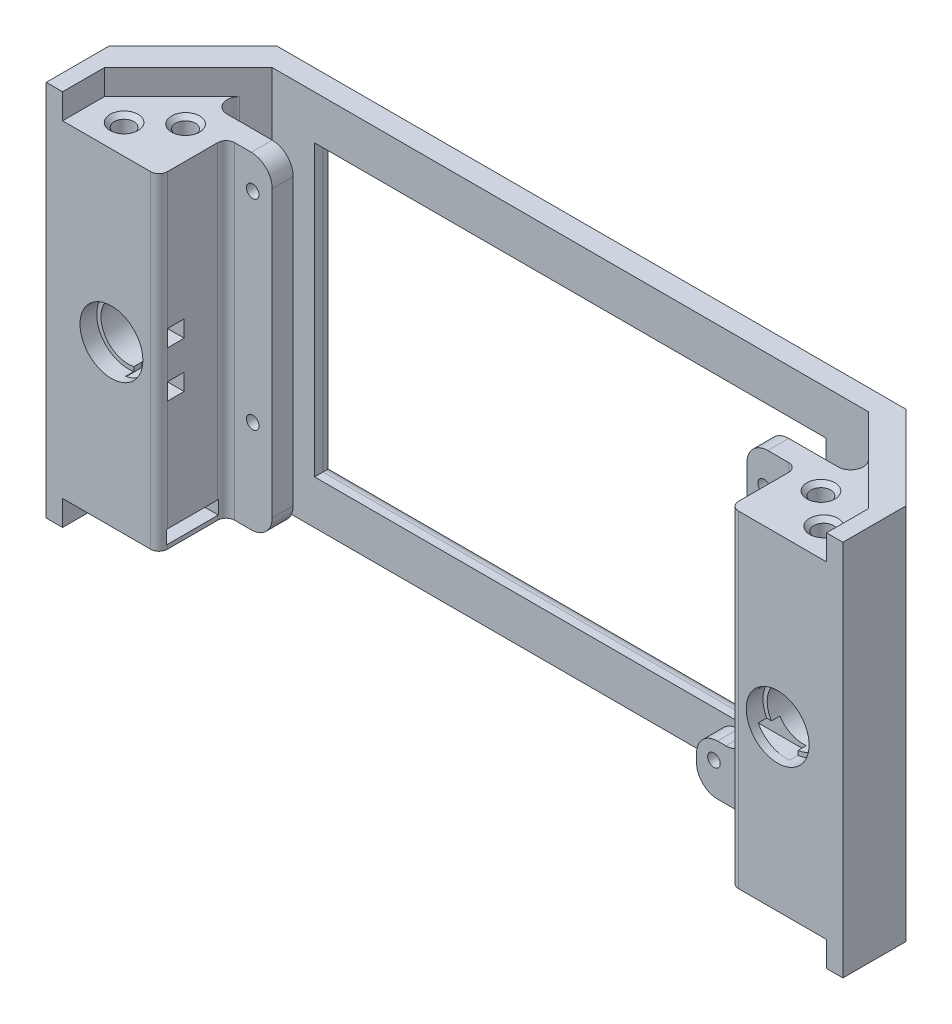
SolidWorks part; units mm, degrees
ref_plane "Front Plane" through (0, 0, 0) normal (0, 0, 1) x (1, 0, 0)
ref_plane "Top Plane" through (0, 0, 0) normal (0, 1, 0) x (1, 0, 0)
ref_plane "Right Plane" through (0, 0, 0) normal (1, 0, 0) x (0, 0, -1)
sketch "Sketch1" plane through (0, 0, 0) normal (0, 0, 1) x (1, 0, 0)
  line L1 (-95, 45) -> (95, 45)
  line L2 (-95, 45) -> (-95, -45)
  line L3 (-95, -45) -> (95, -45)
  line L4 (95, 45) -> (95, -45)
  line L5 (-95, 45) -> (95, -45) construction
  line L6 (-95, -45) -> (95, 45) construction
  line L7 (-61, 34.5) -> (61, 34.5)
  line L8 (-61, 34.5) -> (-61, -34.5)
  line L9 (-61, -34.5) -> (61, -34.5)
  line L10 (61, 34.5) -> (61, -34.5)
  line L11 (-61, 34.5) -> (61, -34.5) construction
  line L12 (-61, -34.5) -> (61, 34.5) construction
  point P0 (0, 0)
  point P6 (0, 0)
  dimension "D1" = 122
  dimension "D2" = 190
  dimension "D3" = 69
  dimension "D4" = 90
extrude "Boss-Extrude1" add sketch "Sketch1" along normal blind 5
sketch "Sketch2" plane through (0, 0, 5) normal (0, 0, 1) x (1, 0, 0)
  line L0 (-95, -45) -> (95, -45) construction
  line L1 (-95, 45) -> (-91.1, 45)
  line L2 (-95, 45) -> (-95, -45)
  line L3 (-95, -45) -> (-91.1, -45)
  line L4 (-91.1, 45) -> (-91.1, -45)
  line L5 (0, 0) -> (0, 45) construction
  line L6 (95, 45) -> (-95, 45) construction
  line L7 (95, -45) -> (91.1, -45)
  line L8 (91.1, 45) -> (91.1, -45)
  line L9 (95, 45) -> (91.1, 45)
  line L10 (95, 45) -> (95, -45)
  dimension "D1" = 3.9
extrude "Boss-Extrude2" add sketch "Sketch2" along normal blind 30
sketch "Sketch3" plane through (0, 45, 0) normal (0, 1, 0) x (1, 0, 0)
  line L0 (-91.1, -35) -> (-91.1, -5) construction
  line L1 (-91.1, -14) -> (-57.1, -14)
  line L2 (-91.1, -14) -> (-91.1, -19)
  line L3 (-91.1, -19) -> (-57.1, -19)
  line L4 (-57.1, -14) -> (-57.1, -19)
  line L5 (91.1, -35) -> (91.1, -5) construction
  line L6 (91.1, -14) -> (44.1, -14)
  line L7 (91.1, -14) -> (91.1, -19)
  line L8 (91.1, -19) -> (44.1, -19)
  line L9 (44.1, -14) -> (44.1, -19)
  line L10 (91.1, -5) -> (-91.1, -5) construction
  dimension "D1" = 9
  dimension "D2" = 9
  dimension "D3" = 5
  dimension "D4" = 5
  dimension "D5" = 34
  dimension "D6" = 47
extrude "Boss-Extrude3" add sketch "Sketch3" against normal up to surface (90 mm away) up to face at (0, -45, 18.75)
sketch "Sketch4" plane through (0, 0, 19) normal (0, 0, 1) x (1, 0, 0)
  line L0 (91.1, -45) -> (91.1, 45) construction
  line L1 (-91.1, 45) -> (91.1, 45)
  line L2 (-91.1, 45) -> (-91.1, 39)
  line L3 (-91.1, 39) -> (91.1, 39)
  line L4 (91.1, 45) -> (91.1, 39)
  line L5 (0, 0) -> (-91.1, 0) construction
  line L6 (-91.1, -45) -> (-91.1, 45) construction
  line L7 (-91.1, -39) -> (91.1, -39)
  line L8 (91.1, -45) -> (91.1, -39)
  line L9 (-91.1, -45) -> (91.1, -45)
  line L10 (-91.1, -45) -> (-91.1, -39)
  dimension "D1" = 6
extrude "Cut-Extrude1" cut sketch "Sketch4" against normal blind 5
sketch "Sketch5" plane through (0, 0, 19) normal (0, 0, 1) x (1, 0, 0)
  line L0 (0, 0) -> (-61.75, 0) construction
  line L1 (-70.2, 37.38) -> (70.2, 37.38) construction
  line L2 (-70.2, 37.38) -> (-70.2, -37.38) construction
  line L3 (-70.2, -37.38) -> (70.2, -37.38) construction
  line L4 (70.2, 37.38) -> (70.2, -37.38) construction
  line L5 (-70.2, 37.38) -> (70.2, -37.38) construction
  line L6 (-70.2, -37.38) -> (70.2, 37.38) construction
  line L7 (-61.75, 0) -> (-61.75, 31.13) construction
  line L8 (-61.75, 0) -> (-61.75, -16.61) construction
  line L9 (48.25, 0) -> (60.23, 0) construction
  line L10 (60.23, 0) -> (60.23, 31.13) construction
  line L11 (0, 0) -> (48.25, 0) construction
  line L12 (48.25, 0) -> (48.25, -31.38) construction
  circle A0 centre (-61.75, 31.13) radius 1.5
  circle A1 centre (-61.75, -16.61) radius 1.5
  circle A2 centre (60.23, 31.13) radius 1.5
  circle A3 centre (48.25, -31.38) radius 1.5
  point P0 (0, 0)
  dimension "D10" = 3
  dimension "D11" = 3
  dimension "D12" = 3
  dimension "D13" = 3
  dimension "D1" = 140.4
  dimension "D2" = 74.76
  dimension "D3" = 61.75
  dimension "D4" = 31.13
  dimension "D5" = 16.61
  dimension "D6" = 60.23
  dimension "D7" = 31.13
  dimension "D8" = 48.25
  dimension "D9" = 31.38
extrude "Cut-Extrude2" cut sketch "Sketch5" against normal up to surface (5 mm away) up to face at (67.6, 0, 14)
sketch "Sketch6" plane through (0, 0, 19) normal (0, 0, 1) x (1, 0, 0)
  line L1 (44.1, 39) -> (56.1, 39)
  line L2 (44.1, 39) -> (44.1, -27)
  line L3 (44.1, -27) -> (56.1, -27)
  line L4 (56.1, 39) -> (56.1, -27)
  dimension "D1" = 12
  dimension "D2" = 66
extrude "Cut-Extrude3" cut sketch "Sketch6" against normal up to surface (5 mm away) up to face at (46.75, -31.38, 14)
fillet "Fillet3" radius 3 4 edges at (-61, 0, 0) (0, -34.5, 0) (61, 0, 0) (0, 34.5, 0)
chamfer "Chamfer6" distance 20 angle 45 4 edges at (91.1, 0, 5) (95, 0, 0) (-95, 0, 0) (-91.1, 0, 5)
sketch "Sketch7" plane through (0, 39, 0) normal (0, 1, 0) x (1, 0, 0)
  line L0 (-85.1, -19) -> (-91.1, -25)
  line L1 (-91.1, -25) -> (-91.1, -35)
  line L2 (-91.1, -35) -> (-68.1, -35)
  line L3 (-68.1, -35) -> (-68.1, -19)
  line L4 (-85.1, -19) -> (-57.1, -19) construction
  line L5 (-68.1, -19) -> (-85.1, -19)
  line L6 (0, 0) -> (0, -5) construction
  line L7 (71.1, -5) -> (-71.1, -5) construction
  line L8 (68.1, -35) -> (68.1, -19)
  line L9 (91.1, -35) -> (68.1, -35)
  line L10 (91.1, -25) -> (91.1, -35)
  line L11 (85.1, -19) -> (91.1, -25)
  line L12 (68.1, -19) -> (85.1, -19)
  dimension "D1" = 23
extrude "Boss-Extrude4" add sketch "Sketch7" against normal up to surface (78 mm away) up to face at (-69.85, -39, 16.5)
fillet "Fillet4" radius 5 6 edges at (-57.1, -39, 16.5) (-57.1, 39, 16.5) (56.1, 39, 16.5) (44.1, -39, 16.5) (44.1, -27, 16.5) (56.1, -27, 16.5)
fillet "Fillet5" radius 2 4 edges at (-68.1, 0, 35) (68.1, 0, 35) (68.1, 0, 19) (-68.1, 0, 19)
fillet "Fillet6" radius 3 2 edges at (-80.1, 0, 14) (80.1, 0, 14)
sketch "Sketch9" plane through (0, 0, 35) normal (0, 0, 1) x (1, 0, 0)
  line L6 (0, 0) -> (0, -45) construction
  line L7 (-71.1, -45) -> (71.1, -45) construction
  line L8 (-95, 45) -> (-95, -45) construction
  line L9 (-95, 39) -> (-79.45, 39) construction
  line L10 (-95, 39) -> (-95, -0.9074) construction
  line L11 (-95, -0.9074) -> (-79.45, -0.9074) construction
  line L12 (-79.45, 39) -> (-79.45, -0.9074) construction
  line L13 (-91.1, 39) -> (-70.1, 39) construction
  circle A0 centre (-79.45, -0.9074) radius 6.5
  circle A1 centre (79.45, -0.9074) radius 6.5
  dimension "D3" = 13
  dimension "D1" = 39.9074
  dimension "D2" = 15.55
extrude "Cut-Extrude4" cut sketch "Sketch9" against normal blind 10
sketch "Sketch10" plane through (0, 0, 35) normal (0, 0, 1) x (1, 0, 0)
  circle A0 centre (-79.45, -0.9074) radius 7.5
  circle A1 centre (79.45, -0.9074) radius 7.5
  dimension "D1" = 15
  dimension "D2" = 15
extrude "Cut-Extrude5" cut sketch "Sketch10" against normal blind 4
sketch "Sketch12" plane through (-68.1, 0, 0) normal (1, 0, 0) x (0, 0, -1)
  line L0 (-33, -4.4074) -> (-29, -4.4074)
  line L1 (-33, 39) -> (-23, 39) construction
  line L2 (-33, 39) -> (-33, -0.9074) construction
  line L3 (-33, -0.9074) -> (-23, -0.9074) construction
  line L4 (-23, 39) -> (-23, -0.9074) construction
  line L5 (-33, 6.5926) -> (-23, 6.5926) construction
  line L6 (-33, 6.5926) -> (-33, -8.4074) construction
  line L7 (-33, -8.4074) -> (-23, -8.4074) construction
  line L8 (-23, 6.5926) -> (-23, -8.4074) construction
  line L9 (-33, 6.5926) -> (-23, -8.4074) construction
  line L10 (-33, -8.4074) -> (-23, 6.5926) construction
  line L11 (-33, 6.5926) -> (-29, 6.5926)
  line L12 (-33, 6.5926) -> (-33, 2.5926)
  line L13 (-33, 2.5926) -> (-29, 2.5926)
  line L14 (-29, 6.5926) -> (-29, 2.5926)
  line L15 (-29, -8.4074) -> (-29, -4.4074)
  line L16 (-33, -8.4074) -> (-29, -8.4074)
  line L17 (-33, -8.4074) -> (-33, -4.4074)
  point P5 (-28, -0.9074)
  dimension "D1" = 39.9074
  dimension "D2" = 10
  dimension "D3" = 15
  dimension "D4" = 10
  dimension "D5" = 4
  dimension "D6" = 4
extrude "Cut-Extrude6" cut sketch "Sketch12" against normal blind 10 and the other way blind 148.4
sketch "Sketch15" plane through (0, 39, 0) normal (0, 1, 0) x (1, 0, 0)
  line L0 (68.1, -21) -> (68.1, -33) construction
  line L5 (72.8574, -14) -> (61.1, -14) construction
  line L6 (91.1, -35) -> (68.1, -35) construction
  line L7 (91.1, -35) -> (91.1, -14) construction
  line L8 (91.1, -14) -> (68.1, -14) construction
  line L9 (68.1, -35) -> (68.1, -14) construction
  line L10 (68.1, -14) -> (75.7667, -21) construction
  line L11 (75.7667, -21) -> (83.4333, -28) construction
  line L12 (83.4333, -28) -> (91.1, -35) construction
  line L13 (0, 0) -> (0, -5) construction
  line L14 (71.1, -5) -> (-71.1, -5) construction
  circle A0 centre (75.7667, -21) radius 2.35
  circle A1 centre (83.4333, -28) radius 2.35
  circle A2 centre (-75.7667, -21) radius 2.35
  circle A3 centre (-83.4333, -28) radius 2.35
  dimension "D1" = 4.7
  dimension "D2" = 4.7
  dimension "D3" = 23
  dimension "D4" = 21
extrude "Cut-Extrude7" cut sketch "Sketch15" against normal blind 8
chamfer "Chamfer7" distance 1 angle 45 4 edges at (-83.4333, 39, 25.65) (-75.7667, 39, 18.65) (83.4333, 39, 30.35) (75.7667, 39, 23.35)
sketch "Sketch17" plane through (0, -39, 0) normal (0, -1, 0) x (1, 0, 0)
  line L0 (0, 0) -> (0, 5) construction
  line L1 (91.1, 35) -> (68.1, 35) construction
  line L2 (91.1, 35) -> (91.1, 19) construction
  line L3 (91.1, 19) -> (68.1, 19) construction
  line L4 (68.1, 35) -> (68.1, 19) construction
  line L5 (-71.1, 5) -> (71.1, 5) construction
  line L6 (68.1, 33) -> (68.1, 21) construction
  line L7 (66.1, 19) -> (49.1, 19) construction
  circle A0 centre (79.6, 27) radius 4
  circle A1 centre (-79.6, 27) radius 4
  dimension "D2" = 8
  dimension "D1" = 11.5
  dimension "D3" = 8
extrude "Cut-Extrude8" cut sketch "Sketch17" against normal blind 4.2
sketch "Sketch18" plane through (68.1, 0, 0) normal (-1, 0, 0) x (0, 0, 1)
  line L5 (27, -38) -> (27, -34.8) construction
  line L6 (33.15, -34.8) -> (20.85, -34.8)
  line L7 (33.15, -34.8) -> (33.15, -38)
  line L8 (33.15, -38) -> (20.85, -38)
  line L9 (20.85, -34.8) -> (20.85, -38)
  line L11 (27, -39) -> (27, -34.8) construction
  line L12 (33, -39) -> (21, -39) construction
  dimension "D1" = 4.2
  dimension "D2" = 12.3
  dimension "D3" = 3.2
extrude "Cut-Extrude9" cut sketch "Sketch18" against normal blind 17.6 and the other way blind 153.8
